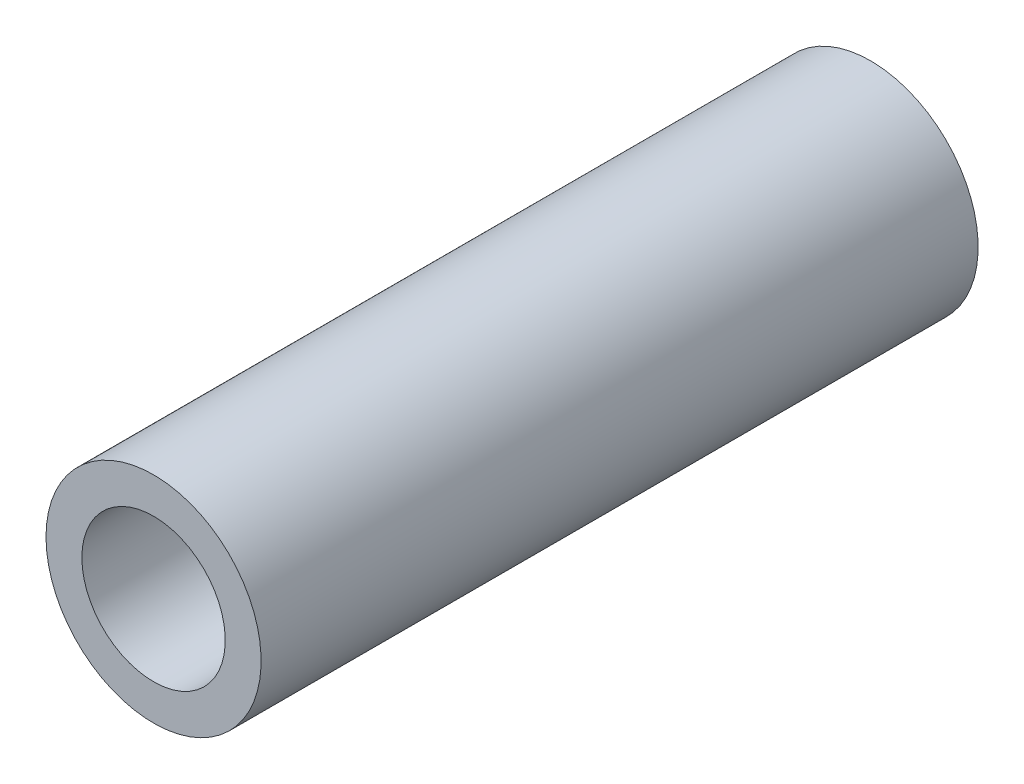
SolidWorks part; units mm, degrees
material "ABS"
ref_plane "Front Plane" through (0, 0, 0) normal (0, 0, 1) x (1, 0, 0)
ref_plane "Top Plane" through (0, 0, 0) normal (0, 1, 0) x (1, 0, 0)
ref_plane "Right Plane" through (0, 0, 0) normal (1, 0, 0) x (0, 0, -1)
sketch "Sketch1" plane through (0, 0, 0) normal (0, 0, 1) x (1, 0, 0)
  circle A0 centre (0, 0) radius 3
  circle A1 centre (0, 0) radius 2
  dimension "D1" = 6
  dimension "D2" = 4
extrude "Boss-Extrude1" add sketch "Sketch1" along normal blind 20
extrude "Boss-Extrude2" add sketch "Sketch1<2>" along normal blind 10 contours A1
sketch "Sketch1<2>" plane through (0, 0, 0) normal (0, 0, 1) x (1, 0, 0) same geometry as "Sketch1"
